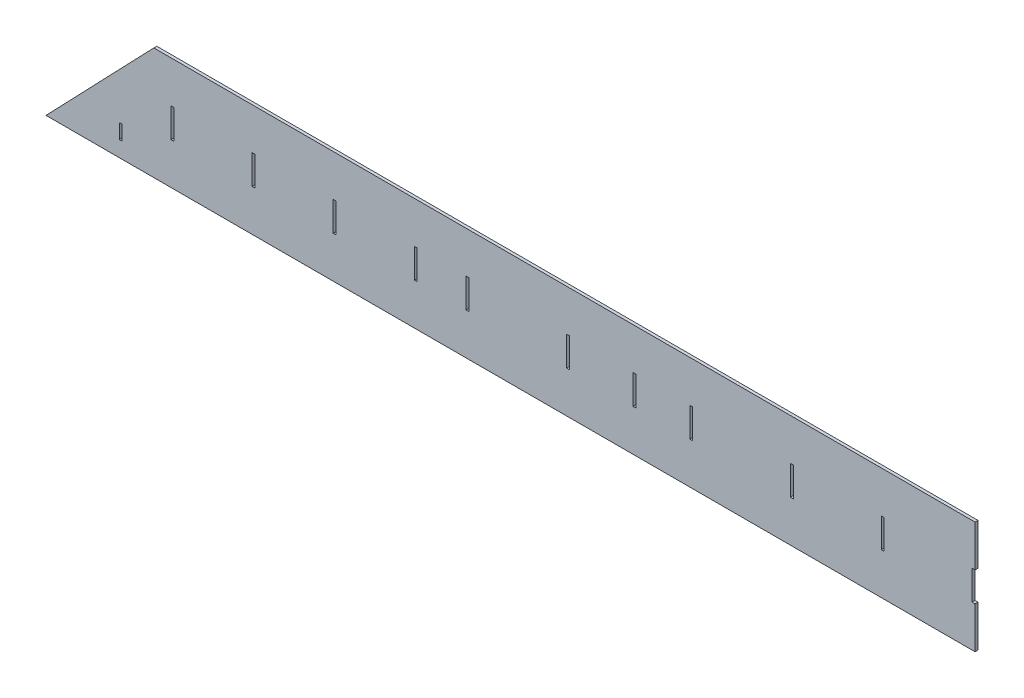
SolidWorks part; units mm, degrees
ref_plane "Front Plane" through (0, 0, 0) normal (0, 0, 1) x (1, 0, 0)
ref_plane "Top Plane" through (0, 0, 0) normal (0, 1, 0) x (1, 0, 0)
ref_plane "Right Plane" through (0, 0, 0) normal (1, 0, 0) x (0, 0, -1)
sketch "Sketch1" plane through (0, 0, 0) normal (0, 0, 1) x (1, 0, 0)
  line L0 (0, 0) -> (110.3511, 115)
  line L1 (110.3511, 115) -> (951, 115)
  line L2 (948, 72.5) -> (948, 42.5)
  line L3 (951, 0) -> (0, 0)
  line L4 (1244.614, 57.5) -> (-683.0281, 57.5) construction
  line L5 (128, 72.5) -> (131, 72.5)
  line L6 (128, 72.5) -> (128, 42.5)
  line L7 (128, 42.5) -> (131, 42.5)
  line L8 (131, 72.5) -> (131, 42.5)
  line L9 (75, 31.1091) -> (78, 31.1091)
  line L10 (75, 31.1091) -> (75, 16.1091)
  line L11 (75, 16.1091) -> (78, 16.1091)
  line L12 (78, 31.1091) -> (78, 16.1091)
  line L13 (948, 72.5) -> (951, 72.5)
  line L14 (211, 72.5) -> (214, 72.5)
  line L15 (211, 72.5) -> (211, 42.5)
  line L16 (211, 42.5) -> (214, 42.5)
  line L17 (214, 72.5) -> (214, 42.5)
  line L18 (294, 72.5) -> (297, 72.5)
  line L19 (294, 72.5) -> (294, 42.5)
  line L20 (294, 42.5) -> (297, 42.5)
  line L21 (297, 72.5) -> (297, 42.5)
  line L22 (377, 72.5) -> (380, 72.5)
  line L23 (377, 72.5) -> (377, 42.5)
  line L24 (377, 42.5) -> (380, 42.5)
  line L25 (380, 72.5) -> (380, 42.5)
  line L26 (430, 72.5) -> (433, 72.5)
  line L27 (430, 72.5) -> (430, 42.5)
  line L28 (430, 42.5) -> (433, 42.5)
  line L29 (433, 72.5) -> (433, 42.5)
  line L30 (533, 72.5) -> (536, 72.5)
  line L31 (533, 72.5) -> (533, 42.5)
  line L32 (533, 42.5) -> (536, 42.5)
  line L33 (536, 72.5) -> (536, 42.5)
  line L34 (601, 72.5) -> (604, 72.5)
  line L35 (601, 72.5) -> (601, 42.5)
  line L36 (601, 42.5) -> (604, 42.5)
  line L37 (604, 72.5) -> (604, 42.5)
  line L38 (659, 72.5) -> (662, 72.5)
  line L39 (659, 72.5) -> (659, 42.5)
  line L40 (659, 42.5) -> (662, 42.5)
  line L41 (662, 72.5) -> (662, 42.5)
  line L42 (762, 72.5) -> (765, 72.5)
  line L43 (762, 72.5) -> (762, 42.5)
  line L44 (762, 42.5) -> (765, 42.5)
  line L45 (765, 72.5) -> (765, 42.5)
  line L46 (855, 72.5) -> (858, 72.5)
  line L47 (855, 72.5) -> (855, 42.5)
  line L48 (855, 42.5) -> (858, 42.5)
  line L49 (858, 72.5) -> (858, 42.5)
  line L50 (951, 72.5) -> (951, 115)
  line L51 (948, 42.5) -> (951, 42.5)
  line L52 (951, 42.5) -> (951, 0)
  point P43 (0, 0)
  point P57 (0, 0)
  point P58 (0, 0)
  dimension "D1" = 115
  dimension "D2" = 30
  dimension "D3" = 3
  dimension "D4" = 15
  dimension "D5" = 3
  dimension "D6" = 75
  dimension "D7" = 50
  dimension "D8" = 30
  dimension "D9" = 3
  dimension "D10" = 30
  dimension "D11" = 3
  dimension "D12" = 80
  dimension "D13" = 80
  dimension "D14" = 80
  dimension "D15" = 3
  dimension "D16" = 30
  dimension "D17" = 50
  dimension "D18" = 3
  dimension "D19" = 30
  dimension "D20" = 100
  dimension "D21" = 3
  dimension "D22" = 30
  dimension "D23" = 65
  dimension "D24" = 30
  dimension "D25" = 3
  dimension "D26" = 55
  dimension "D27" = 3
  dimension "D28" = 30
  dimension "D29" = 3
  dimension "D30" = 30
  dimension "D31" = 100
  dimension "D32" = 90
  dimension "D33" = 3
  dimension "D34" = 30
  dimension "D35" = 3
  dimension "D36" = 30
  dimension "D37" = 90
  dimension "D38" = 3
extrude "Boss-Extrude1" add sketch "Sketch1" along normal blind 3
